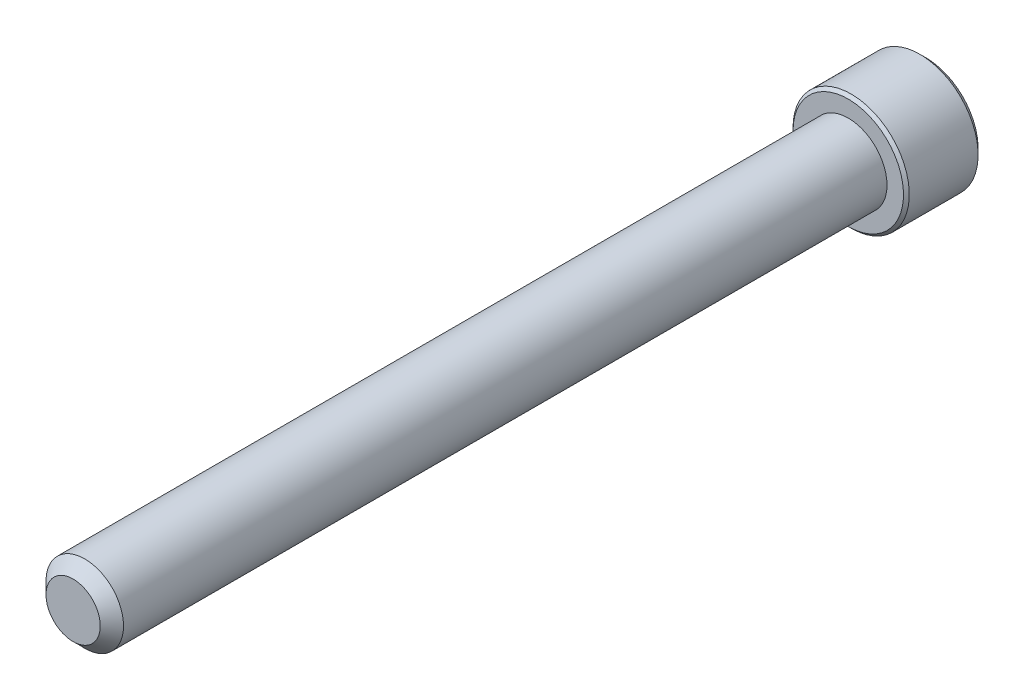
SolidWorks part; units mm, degrees
ref_plane "Front Plane" through (0, 0, 0) normal (0, 0, 1) x (1, 0, 0)
ref_plane "Top Plane" through (0, 0, 0) normal (0, 1, 0) x (1, 0, 0)
ref_plane "Right Plane" through (0, 0, 0) normal (1, 0, 0) x (0, 0, -1)
sketch "Sketch0" plane through (0, 0, 0) normal (1, 0, 0) x (0, 0, -1)
  line L0 (0, 0) -> (63.5, 0) construction
  point P2 (69.85, 0)
  point P4 (25.4, 0)
  dimension "D1" = 63.5
  dimension "D2" = 6.35
  dimension "Min Thread" = 25.4
sketch "Sketch1" plane through (0, 0, 0) normal (0, 0, 1) x (1, 0, 0)
  circle A0 centre (0, 0) radius 3.175
  dimension "OD" = 6.35
extrude "Extrude1" add sketch "Sketch1" against normal blind 63.5
sketch "Sketch2" plane through (0, 0, 0) normal (0, 0, 1) x (1, 0, 0)
  circle A0 centre (0, 0) radius 3.175 construction
  circle A1 centre (0, 0) radius 3.175
curve "Helix/Spiral1" pitch 1.27 height 64.77 turns 51 parameters "pitch"=1.27
chamfer "Chamfer3" distance 0.9525 angle 45 1 edges at (3.175, 0, 0)
sketch "Sketch3" plane through (0, 0, 0) normal (1, 0, 0) x (0, 0, -1)
  line L0 (-1.1113, 3.175) -> (-0.635, 2.3501)
  line L1 (-0.635, 2.3501) -> (-0.4763, 2.3501)
  line L2 (-0.4763, 2.3501) -> (0, 3.175)
  line L3 (-1.1113, 3.175) -> (0, 3.175)
  line L4 (-0.5556, 3.175) -> (-0.5556, 2.3501) construction
  line L5 (-0.8731, 2.7626) -> (-0.2381, 2.7626) construction
  line L6 (0, 3.175) -> (0, -3.175) construction
  dimension "D2" = 0.635
  dimension "D3" = 60
sweep "Cut-Sweep1" [suppressed] cut profiles "Sketch3" path "Helix/Spiral1"
sketch "Sketch5" [suppressed] plane through (0, 0, 0) normal (1, 0, 0) x (0, 0, -1)
  line L0 (63.5, -2.3728) -> (63.5, 2.2654) construction
  line L1 (63.5, 3.175) -> (25.4, 3.175)
  line L2 (63.5, 3.175) -> (63.5, 0)
  line L3 (63.5, 0) -> (24.2444, 0)
  line L4 (0, 0) -> (63.5, 0) construction
  line L5 (25.4, 3.175) -> (24.2444, 0)
  line L6 (0, 0) -> (66.04, 0) construction
  dimension "D1" = 70
  dimension "D3" = 2.54
revolve "partially thread" [suppressed] add sketch "Sketch5" angle 360 about L6
sketch "Sketch6" plane through (0, 0, -63.5) normal (0, 0, -1) x (-1, 0, 0)
  circle A0 centre (0, 0) radius 4.7625
  dimension "head dia" = 9.525
extrude "Extrude2" add sketch "Sketch6" along normal blind 6.35
sketch "Sketch7" plane through (0, 0, -69.85) normal (0, 0, -1) x (-1, 0, 0)
  line L1 (0, 2.7496) -> (-2.3813, 1.3748)
  line L2 (-2.3813, 1.3748) -> (-2.3813, -1.3748)
  line L3 (-2.3813, -1.3748) -> (0, -2.7496)
  line L4 (0, -2.7496) -> (2.3813, -1.3748)
  line L5 (2.3813, -1.3748) -> (2.3813, 1.3748)
  line L6 (2.3813, 1.3748) -> (0, 2.7496)
  circle A0 centre (0, 0) radius 2.3813 construction
  dimension "hex dia" = 4.7625
extrude "Cut-Extrude1" cut sketch "Sketch7" against normal blind 3.5719
sketch "Sketch8" plane through (0, 0, -69.85) normal (0, 0, -1) x (-1, 0, 0)
  circle A0 centre (0, 0) radius 2.7496
extrude "Cut-Extrude2" cut sketch "Sketch8" against normal through all draft 45
chamfer "Chamfer1" distance 0.4763 angle 45 1 edges at (-4.7625, 0, -69.85)
chamfer "Chamfer2" distance 0.2381 angle 45 1 edges at (-4.7625, 0, -63.5)
sketch "Sketch9" plane through (0, 0, 0) normal (1, 0, 0) x (0, 0, -1)
  line L0 (0, 3.175) -> (0, -3.175) construction
  line L1 (3.175, 3.175) -> (3.175, -3.175) construction
  line L2 (69.85, 4.7625) -> (69.85, -4.7625) construction
  line L3 (63.5, 4.7625) -> (63.5, -4.7625) construction
  line L4 (63.5, 4.5244) -> (63.5, -4.5244) construction
  line L5 (69.85, -4.2862) -> (69.85, 4.2862) construction
  line L6 (63.5, -4.7625) -> (63.5, 4.7625) construction
  line L7 (0, 2.2225) -> (0, -2.2225) construction
  line L8 (-1.1113, 3.175) -> (0, 3.175) construction
  line L9 (3.175, 0) -> (0, 0) construction
  dimension "D1" = 3.175
equation "\"D3@Helix/Spiral1\" = \"screw length@Extrude1\"+\"pitch@Helix/Spiral1\""
equation "\"D1@Sketch3\" = \"pitch@Helix/Spiral1\"*.125"
equation "\"D2@Sketch3\" = \"pitch@Helix/Spiral1\"*.5"
equation "\"D1@Cut-Extrude1\" = \"hex dia@Sketch7\"*.75"
equation "\"D1@Chamfer1\" = \"head dia@Sketch6\"*.05"
equation "\"D1@Sketch9\" = \"pitch@Helix/Spiral1\"*2.50"
equation "\"D1@Chamfer2\" = \"D1@Chamfer1\"/2"
equation "\"D1@Chamfer3\" = \"pitch@Helix/Spiral1\"*.750"
equation "\"D1@Sketch0\" = \"screw length@Extrude1\""
equation "\"D2@Sketch0\" = \"head depth@Extrude2\""
